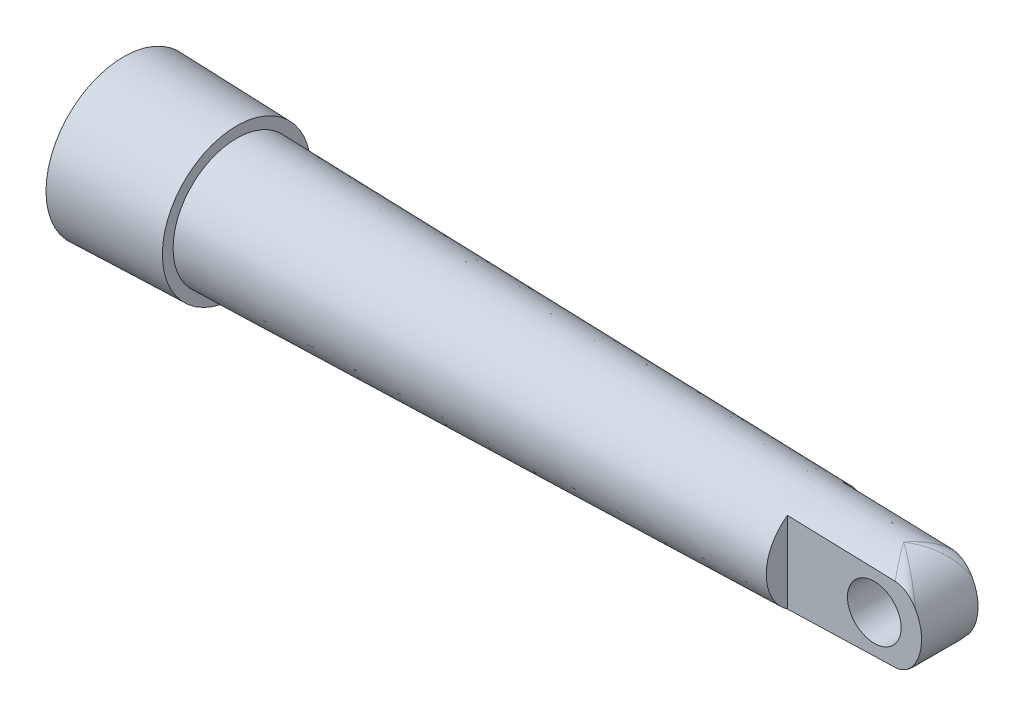
SolidWorks part; units mm, degrees
ref_plane "Front Plane" through (0, 0, 0) normal (0, 0, 1) x (1, 0, 0)
ref_plane "Top Plane" through (0, 0, 0) normal (0, 1, 0) x (1, 0, 0)
ref_plane "Right Plane" through (0, 0, 0) normal (1, 0, 0) x (0, 0, -1)
sketch "Sketch1" plane through (0, 0, 0) normal (0, 0, 1) x (1, 0, 0)
  line L0 (0, 0) -> (24.5, 0)
  line L1 (24.5, 0) -> (24.5, 1.75)
  line L2 (24.5, 1.75) -> (4, 2.25)
  line L3 (4, 2.25) -> (4, 2.63)
  line L4 (4, 2.63) -> (0, 2.75)
  line L5 (0, 2.75) -> (0, 0)
  dimension "D1" = 2.75
  dimension "D2" = 2.63
  dimension "D3" = 2.25
  dimension "D4" = 1.75
  dimension "D5" = 24.5
  dimension "D6" = 4
revolve "Revolve1" add sketch "Sketch1" angle 360 about L0
sketch "Sketch2" plane through (0, 0, 0) normal (0, 0, 1) x (1, 0, 0)
  line L0 (24.5, 0) -> (33.601, 0) construction
  line L1 (24.5, -1.75) -> (24.5, 1.75) construction
  line L2 (24.5, 1.75) -> (27.6163, 1.674)
  line L3 (27.6163, -1.674) -> (24.5, -1.75)
  line L4 (24.5, 1.75) -> (4, 2.25) construction
  line L5 (4, -2.25) -> (24.5, -1.75) construction
  line L6 (24.5, 1.75) -> (24.5, -1.75)
  arc A0 (27.6163, 1.674) -> (27.6163, -1.674) centre (27.5755, 0) cw
  point P16 (29.25, 0)
  dimension "D1" = 4.75
extrude "Boss-Extrude1" add sketch "Sketch2" along normal mid plane 2
sketch "Sketch3" plane through (0, 0, 0) normal (0, 0, 1) x (1, 0, 0)
  line L0 (24.5, 1.75) -> (24.5, 2.5)
  line L1 (24.5, 2.5) -> (30.1562, 2.5)
  line L2 (30.1562, 2.5) -> (30.1562, 1.612)
  line L3 (30.1562, 1.612) -> (24.5, 1.75)
  line L4 (27.6163, 1.674) -> (24.5, 1.75) construction
  line L5 (24.5, 0) -> (32.2787, 0) construction
  line L6 (24.5, -1.4361) -> (24.5, 1.4361) construction
  dimension "D1" = 2.5
revolve "Cut-Revolve1" cut sketch "Sketch3" angle 360 about L5
sketch "Sketch4" plane through (0, 0, 1) normal (0, 0, 1) x (1, 0, 0)
  circle A0 centre (27.5755, 0) radius 0.95
  dimension "D1" = 1.9
extrude "Cut-Extrude1" cut sketch "Sketch4" against normal through all both and the other way through all
fillet "Fillet1" radius 0.5 2 edges at (28.3737, 1.472, -0.7575) (28.0769, 1.5977, 0.4607)
fillet "Fillet2" radius 0.5 2 edges at (28.0769, -1.5977, -0.4607) (28.3737, -1.472, 0.7575)
sketch "Sketch5" plane through (0, 0, 0) normal (-1, 0, 0) x (0, 0, 1)
  circle A0 centre (0, 0) radius 1
  dimension "D1" = 2
extrude "Cut-Extrude2" cut sketch "Sketch5" against normal blind 15
